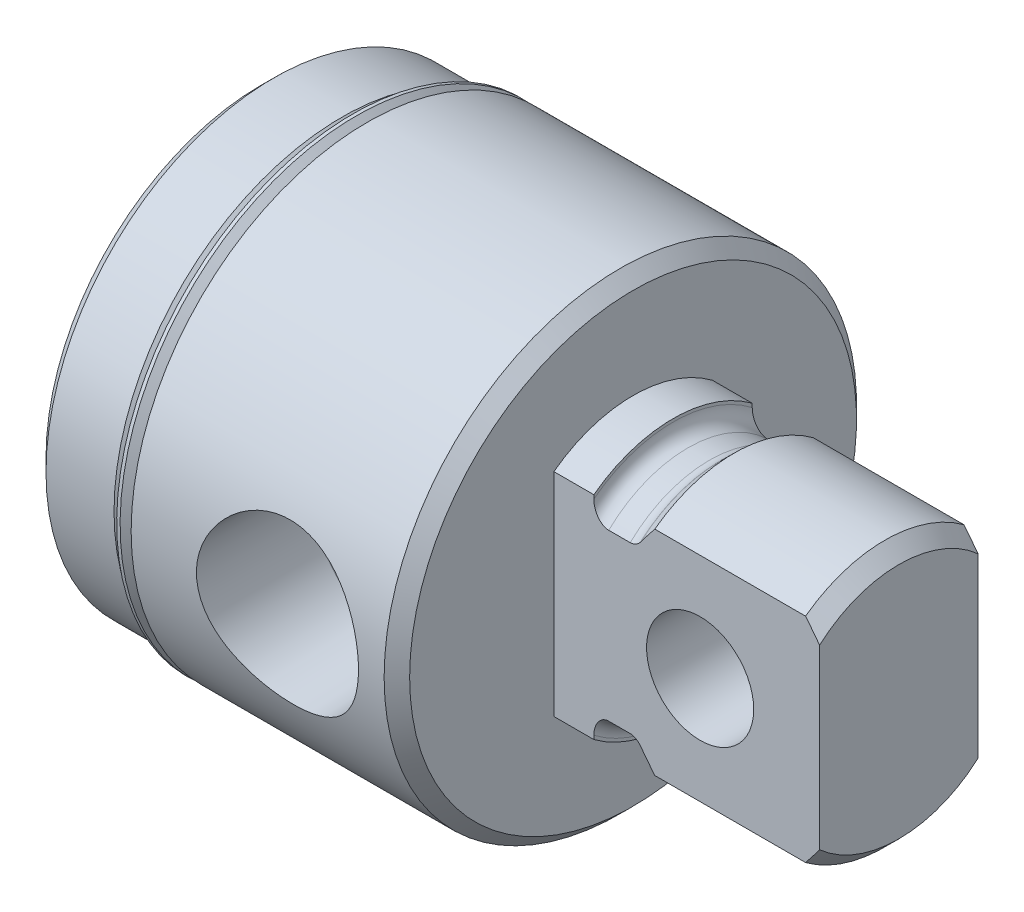
SolidWorks part; units mm, degrees
material "Cast Alloy Steel"
ref_plane "Front Plane" through (0, 0, 0) normal (0, 0, 1) x (1, 0, 0)
ref_plane "Top Plane" through (0, 0, 0) normal (0, 1, 0) x (1, 0, 0)
ref_plane "Right Plane" through (0, 0, 0) normal (1, 0, 0) x (0, 0, -1)
ref_plane "Plane1" through (38.1, 0, 0) normal (1, 0, 0) x (0, 0, -1)
sketch "Sketch1" plane through (0, 0, 0) normal (0, 0, 1) x (1, 0, 0)
  line L0 (0, 0) -> (0, 12.846)
  line L1 (0, 12.846) -> (0.762, 13.6081)
  line L2 (0.762, 13.6081) -> (4.826, 13.6081)
  line L3 (4.826, 13.6081) -> (5.588, 12.846)
  line L4 (5.588, 12.846) -> (6.35, 12.846)
  line L5 (6.35, 12.846) -> (6.35, 14.1097)
  line L6 (6.35, 14.1097) -> (21.463, 14.1097)
  line L7 (21.463, 14.1097) -> (22.225, 13.3477)
  line L8 (22.225, 13.3477) -> (22.225, 0)
  line L9 (22.225, 0) -> (0, 0)
  line L10 (22.225, 0) -> (0, 0) construction
revolve "Revolve1" add sketch "Sketch1" angle 360 about L10 reverse direction yes
sketch "Sketch2" plane through (0, 0, 0) normal (0, 0, 1) x (1, 0, 0)
  line L0 (22.225, 0) -> (22.225, 7.9057)
  line L1 (22.225, 7.9057) -> (24.6126, 7.9057)
  line L2 (24.6126, 7.9057) -> (24.6126, 7.7279)
  line L3 (25.5016, 6.8389) -> (26.7843, 6.8389)
  line L4 (27.383, 7.0708) -> (27.4129, 7.098)
  line L5 (27.4129, 7.098) -> (28.2524, 7.9375)
  line L6 (28.2524, 7.9375) -> (37.2605, 7.9375)
  line L7 (37.2605, 7.9375) -> (38.1, 7.098)
  line L8 (38.1, 7.098) -> (38.1, 0)
  line L9 (38.1, 0) -> (22.225, 0)
  line L10 (38.1, 0) -> (22.225, 0) construction
  arc A0 (24.6126, 7.7279) -> (25.5016, 6.8389) centre (25.5016, 7.7279) ccw
  arc A1 (26.7843, 6.8389) -> (27.383, 7.0708) centre (26.7843, 7.7279) ccw
revolve "Revolve2" add sketch "Sketch2" angle 360 about L10 reverse direction yes
cosmetic thread "Cosmetic Thread1" parameters "D1"=10.6871, "D2"=14.1961
sketch "Sketch3" plane through (38.1, 0, 0) normal (1, 0, 0) x (0, 0, -1)
  line L0 (-28.2194, -56.4388) -> (28.2194, -56.4388)
  line L1 (28.2194, -56.4388) -> (28.2194, 56.4388)
  line L2 (28.2194, 56.4388) -> (-28.2194, 56.4388)
  line L3 (-28.2194, 56.4388) -> (-28.2194, -56.4388)
  line L4 (-4.7307, -28.2194) -> (4.7307, -28.2194)
  line L5 (4.7307, -28.2194) -> (4.7307, 28.2194)
  line L6 (4.7307, 28.2194) -> (-4.7307, 28.2194)
  line L7 (-4.7307, 28.2194) -> (-4.7307, -28.2194)
extrude "Cut-Extrude1" cut sketch "Sketch3" against normal blind 15.875
ref_plane "Plane2" through (22.225, 0, 0) normal (1, 0, 0) x (0, 0, -1)
hole_wizard "Hole1" positions "Sketch5" profile "Sketch4" legacy
sketch "Sketch5" plane through (0, 0, 0) normal (-1, 0, 0) x (0, 0, 1)
  point P0 (0, 0)
sketch "Sketch4" plane through (0, 0, 0) normal (0, 1, 0) x (0, 0, 1)
  line L0 (0, 0) -> (0, 23.7046)
  line L1 (0, 23.7046) -> (4.7625, 20.955)
  line L2 (4.7625, 20.955) -> (4.7625, 0)
  line L4 (4.7625, 0) -> (0, 0)
  line L6 (0, 23.7046) -> (-4.7625, 20.955) construction
  line L7 (0, -4.2442) -> (0, 117.3081) construction
  dimension "Diameter" = 9.525
  dimension "Depth" = 20.955
  dimension "Drill Angle" = 120
ref_plane "Plane3" through (0, 0, 0) normal (0, 0.9998, 0.0175) x (1, 0, 0)
sketch "Sketch6" plane through (0, 0, 0) normal (0, 0.9998, 0.0175) x (1, 0, 0)
  line L0 (15.0876, 0) -> (19.7106, 0)
  line L1 (19.7106, 0) -> (19.7106, -7.1755)
  line L2 (19.7106, -7.1755) -> (19.9271, -14.1097)
  line L3 (19.9271, -14.1097) -> (15.0876, -14.1097)
  line L4 (15.0876, -14.1097) -> (15.0876, 0)
  line L5 (15.0876, -14.1097) -> (15.0876, 0) construction
revolve "Cut-Revolve1" cut sketch "Sketch6" angle 360 about L5 reverse direction yes
cosmetic thread "Cosmetic Thread2" parameters "D1"=6.9342, "D2"=10.287
ref_plane "Plane4" through (15.0876, 0, 0) normal (1, 0, 0) x (0, 0, -1)
ref_plane "Plane5" through (5.588, 0, 0) normal (1, 0, 0) x (0, 0, -1)
sketch "Sketch7" plane through (0, 0, 0) normal (0, 0, 1) x (1, 0, 0)
  line L0 (5.4861, 14.0255) -> (6.2275, 13.2842)
  line L1 (6.2275, 13.1046) -> (5.969, 12.846)
  line L2 (5.969, 12.846) -> (5.588, 12.846)
  line L3 (5.588, 12.846) -> (5.588, 12.592)
  line L4 (5.588, 12.592) -> (6.35, 12.592)
  line L5 (6.35, 12.592) -> (6.35, 13.449)
  line L6 (6.35, 13.449) -> (5.6893, 14.1097)
  line L7 (5.6893, 14.1097) -> (5.4861, 14.1097)
  line L8 (5.4861, 14.1097) -> (5.4861, 14.0255)
  line L9 (6.35, 0) -> (5.588, 0) construction
  arc A0 (6.2275, 13.2842) -> (6.2275, 13.1046) centre (6.1377, 13.1944) cw
revolve "Revolve3" add sketch "Sketch7" angle 360 about L9 reverse direction yes
ref_plane "Plane6" through (38.227, 0, 0) normal (1, 0, 0) x (0, 0, -1)
sketch "Sketch8" plane through (0, 0, 0) normal (0, 0, 1) x (1, 0, 0)
  circle A0 centre (30.9626, 0) radius 3.2004
extrude "Cut-Extrude2" cut sketch "Sketch8" along normal blind 7.0961 and the other way blind 7.0961
ref_plane "Plane7" through (24.6126, 0, 0) normal (1, 0, 0) x (0, 0, -1)
ref_plane "Plane8" through (33.3248, 0, 0) normal (1, 0, 0) x (0, 0, -1)
ref_plane "Plane9" through (30.9626, 0, 0) normal (1, 0, 0) x (0, 0, -1)
ref_plane "Plane10" through (38.1, 0, 0) normal (1, 0, 0) x (0, 0, -1)
ref_plane "Plane11" through (0, 0, 0) normal (0, 0, 1) x (1, 0, 0)
ref_plane "Plane12" through (24.6126, 0, 0) normal (1, 0, 0) x (0, 0, -1)
ref_plane "Plane13" through (0, 0, 0) normal (0, 1, 0) x (1, 0, 0)
ref_plane "Plane14" through (0, 10.2743, 0) normal (0, 1, 0) x (1, 0, 0)
ref_plane "Plane15" through (22.225, 0, 0) normal (1, 0, 0) x (0, 0, -1)
ref_plane "1 XY" through (24.6126, 0, 0) normal (1, 0, 0) x (0, 0, -1)
ref_plane "1 XZ" through (0, 0, 0) normal (0, -1, 0) x (-1, 0, 0)
ref_plane "1 YZ" through (0, 0, 0) normal (0, 0, -1) x (-1, 0, 0)
ref_axis "1 X" through (24.6126, 0, 80.9) along (0, 0, -1)
ref_axis "1 Y" through (24.6126, -50, 0) along (0, 1, 0)
ref_axis "1 Z" through (80.9, 0, 0) along (-1, 0, 0)
sketch3d "1"
  point P0 (24.6126, 0, 0)
ref_plane "c1 XY" through (0, 0, 0) normal (0, 0, 1) x (1, 0, 0)
ref_plane "c1 XZ" through (0, 7.9057, 0) normal (0, -1, 0) x (-1, 0, 0)
ref_plane "c1 YZ" through (22.225, 0, 0) normal (1, 0, 0) x (0, 0, -1)
ref_axis "c1 X" through (-80.9, 7.9057, 0) along (1, 0, 0)
ref_axis "c1 Y" through (22.225, -50, 0) along (0, 1, 0)
ref_axis "c1 Z" through (22.225, 7.9057, 80.9) along (0, 0, -1)
sketch3d "c1"
  point P0 (22.225, 7.9057, 0)
ref_plane "c2 XY" through (0, 0, 0) normal (0, 0, 1) x (1, 0, 0)
ref_plane "c2 XZ" through (0, -7.9057, 0) normal (0, -1, 0) x (-1, 0, 0)
ref_plane "c2 YZ" through (22.225, 0, 0) normal (1, 0, 0) x (0, 0, -1)
ref_axis "c2 X" through (-80.9, -7.9057, 0) along (1, 0, 0)
ref_axis "c2 Y" through (22.225, -50, 0) along (0, 1, 0)
ref_axis "c2 Z" through (22.225, -7.9057, 80.9) along (0, 0, -1)
sketch3d "c2"
  point P0 (22.225, -7.9057, 0)
ref_plane "cc1 XY" through (0, 0, 0) normal (0, 0, 1) x (1, 0, 0)
ref_plane "cc1 XZ" through (0, 0, 0) normal (0, -1, 0) x (-1, 0, 0)
ref_plane "cc1 YZ" through (22.225, 0, 0) normal (1, 0, 0) x (0, 0, -1)
ref_axis "cc1 X" through (-80.9, 0, 0) along (1, 0, 0)
ref_axis "cc1 Y" through (22.225, -50, 0) along (0, 1, 0)
ref_axis "cc1 Z" through (22.225, 0, 80.9) along (0, 0, -1)
sketch3d "cc1"
  point P0 (22.225, 0, 0)
ref_plane "cc2 XY" through (0, 0, 0) normal (0, 0, 1) x (1, 0, 0)
ref_plane "cc2 XZ" through (0, 0, 0) normal (0, -1, 0) x (-1, 0, 0)
ref_plane "cc2 YZ" through (24.6126, 0, 0) normal (1, 0, 0) x (0, 0, -1)
ref_axis "cc2 X" through (-80.9, 0, 0) along (1, 0, 0)
ref_axis "cc2 Y" through (24.6126, -50, 0) along (0, 1, 0)
ref_axis "cc2 Z" through (24.6126, 0, 80.9) along (0, 0, -1)
sketch3d "cc2"
  point P0 (24.6126, 0, 0)
ref_plane "lovra1 XY" through (33.3248, 0, 0) normal (1, 0, 0) x (0, 0, -1)
ref_plane "lovra1 XZ" through (0, 0, 0) normal (0, -1, 0) x (-1, 0, 0)
ref_plane "lovra1 YZ" through (0, 0, 0) normal (0, 0, -1) x (-1, 0, 0)
ref_axis "lovra1 X" through (33.3248, 0, 80.9) along (0, 0, -1)
ref_axis "lovra1 Y" through (33.3248, -50, 0) along (0, 1, 0)
ref_axis "lovra1 Z" through (80.9, 0, 0) along (-1, 0, 0)
sketch3d "lovra1"
  point P0 (33.3248, 0, 0)
ref_plane "lovra2 XY" through (33.3248, 0, 0) normal (1, 0, 0) x (0, 0, -1)
ref_plane "lovra2 XZ" through (0, 11.049, 0) normal (0, -1, 0) x (-1, 0, 0)
ref_plane "lovra2 YZ" through (0, 0, 0) normal (0, 0, -1) x (-1, 0, 0)
ref_axis "lovra2 X" through (33.3248, 11.049, 80.9) along (0, 0, -1)
ref_axis "lovra2 Y" through (33.3248, -50, 0) along (0, 1, 0)
ref_axis "lovra2 Z" through (80.9, 11.049, 0) along (-1, 0, 0)
sketch3d "lovra2"
  point P0 (33.3248, 11.049, 0)
ref_plane "lovra21 XY" through (0, 0, 0) normal (1, 0, 0) x (0, 0, -1)
ref_plane "lovra21 XZ" through (0, 0, 0) normal (0, -1, 0) x (-1, 0, 0)
ref_plane "lovra21 YZ" through (0, 0, 5.2705) normal (0, 0, -1) x (-1, 0, 0)
ref_axis "lovra21 X" through (0, 0, 80.9) along (0, 0, -1)
ref_axis "lovra21 Y" through (0, -50, 5.2705) along (0, 1, 0)
ref_axis "lovra21 Z" through (80.9, 0, 5.2705) along (-1, 0, 0)
sketch3d "lovra21"
  point P0 (0, 0, 5.2705)
ref_plane "lovra22 XY" through (0, 0, 0) normal (1, 0, 0) x (0, 0, -1)
ref_plane "lovra22 XZ" through (0, 0, 0) normal (0, -1, 0) x (-1, 0, 0)
ref_plane "lovra22 YZ" through (0, 0, -5.2705) normal (0, 0, -1) x (-1, 0, 0)
ref_axis "lovra22 X" through (0, 0, 80.9) along (0, 0, -1)
ref_axis "lovra22 Y" through (0, -50, -5.2705) along (0, 1, 0)
ref_axis "lovra22 Z" through (80.9, 0, -5.2705) along (-1, 0, 0)
sketch3d "lovra22"
  point P0 (0, 0, -5.2705)
ref_plane "lovra3 XY" through (33.3248, 0, 0) normal (1, 0, 0) x (0, 0, -1)
ref_plane "lovra3 XZ" through (0, -11.049, 0) normal (0, -1, 0) x (-1, 0, 0)
ref_plane "lovra3 YZ" through (0, 0, 0) normal (0, 0, -1) x (-1, 0, 0)
ref_axis "lovra3 X" through (33.3248, -11.049, 80.9) along (0, 0, -1)
ref_axis "lovra3 Y" through (33.3248, -50, 0) along (0, 1, 0)
ref_axis "lovra3 Z" through (80.9, -11.049, 0) along (-1, 0, 0)
sketch3d "lovra3"
  point P0 (33.3248, -11.049, 0)
ref_plane "olen XY" through (30.9626, 0, 0) normal (1, 0, 0) x (0, 0, -1)
ref_plane "olen XZ" through (0, 0, 0) normal (0, -1, 0) x (-1, 0, 0)
ref_plane "olen YZ" through (0, 0, 0) normal (0, 0, -1) x (-1, 0, 0)
ref_axis "olen X" through (30.9626, 0, 80.9) along (0, 0, -1)
ref_axis "olen Y" through (30.9626, -50, 0) along (0, 1, 0)
ref_axis "olen Z" through (80.9, 0, 0) along (-1, 0, 0)
sketch3d "olen"
  point P0 (30.9626, 0, 0)
ref_plane "p1 XY" through (38.1, 0, 0) normal (1, 0, 0) x (0, 0, -1)
ref_plane "p1 XZ" through (0, 0, 0) normal (0, -1, 0) x (-1, 0, 0)
ref_plane "p1 YZ" through (0, 0, 4.7307) normal (0, 0, -1) x (-1, 0, 0)
ref_axis "p1 X" through (38.1, 0, 80.9) along (0, 0, -1)
ref_axis "p1 Y" through (38.1, -50, 4.7307) along (0, 1, 0)
ref_axis "p1 Z" through (80.9, 0, 4.7307) along (-1, 0, 0)
sketch3d "p1"
  point P0 (38.1, 0, 4.7307)
ref_plane "p2 XY" through (38.1, 0, 0) normal (1, 0, 0) x (0, 0, -1)
ref_plane "p2 XZ" through (0, 0, 0) normal (0, -1, 0) x (-1, 0, 0)
ref_plane "p2 YZ" through (0, 0, -4.7307) normal (0, 0, -1) x (-1, 0, 0)
ref_axis "p2 X" through (38.1, 0, 80.9) along (0, 0, -1)
ref_axis "p2 Y" through (38.1, -50, -4.7307) along (0, 1, 0)
ref_axis "p2 Z" through (80.9, 0, -4.7307) along (-1, 0, 0)
sketch3d "p2"
  point P0 (38.1, 0, -4.7307)
ref_plane "port XY" through (0, 0, 0) normal (0, 0, 1) x (1, 0, 0)
ref_plane "port XZ" through (0, 0, 0) normal (0, -1, 0) x (-1, 0, 0)
ref_plane "port YZ" through (15.0876, 0, 0) normal (1, 0, 0) x (0, 0, -1)
ref_axis "port X" through (-80.9, 0, 0) along (1, 0, 0)
ref_axis "port Y" through (15.0876, -50, 0) along (0, 1, 0)
ref_axis "port Z" through (15.0876, 0, 80.9) along (0, 0, -1)
sketch3d "port"
  point P0 (15.0876, 0, 0)
ref_plane "port2 XY" through (38.1, 0, 0) normal (1, 0, 0) x (0, 0, -1)
ref_plane "port2 XZ" through (0, 0, 0) normal (0, -1, 0) x (-1, 0, 0)
ref_plane "port2 YZ" through (0, 0, 0) normal (0, 0, -1) x (-1, 0, 0)
ref_axis "port2 X" through (38.1, 0, 80.9) along (0, 0, -1)
ref_axis "port2 Y" through (38.1, -50, 0) along (0, 1, 0)
ref_axis "port2 Z" through (80.9, 0, 0) along (-1, 0, 0)
sketch3d "port2"
  point P0 (38.1, 0, 0)
ref_plane "thd1 XY" through (38.1, 0, 0) normal (1, 0, 0) x (0, 0, -1)
ref_plane "thd1 XZ" through (0, 0, 0) normal (0, -1, 0) x (-1, 0, 0)
ref_plane "thd1 YZ" through (0, 0, 7.9375) normal (0, 0, -1) x (-1, 0, 0)
ref_axis "thd1 X" through (38.1, 0, 80.9) along (0, 0, -1)
ref_axis "thd1 Y" through (38.1, -50, 7.9375) along (0, 1, 0)
ref_axis "thd1 Z" through (80.9, 0, 7.9375) along (-1, 0, 0)
sketch3d "thd1"
  point P0 (38.1, 0, 7.9375)
ref_plane "thd2 XY" through (38.1, 0, 0) normal (1, 0, 0) x (0, 0, -1)
ref_plane "thd2 XZ" through (0, 0, 0) normal (0, -1, 0) x (-1, 0, 0)
ref_plane "thd2 YZ" through (0, 0, -7.9375) normal (0, 0, -1) x (-1, 0, 0)
ref_axis "thd2 X" through (38.1, 0, 80.9) along (0, 0, -1)
ref_axis "thd2 Y" through (38.1, -50, -7.9375) along (0, 1, 0)
ref_axis "thd2 Z" through (80.9, 0, -7.9375) along (-1, 0, 0)
sketch3d "thd2"
  point P0 (38.1, 0, -7.9375)
ref_plane "to_mounting_bracket XY" through (22.225, 0, 0) normal (1, 0, 0) x (0, 0, -1)
ref_plane "to_mounting_bracket XZ" through (0, 0, 0) normal (0, -1, 0) x (-1, 0, 0)
ref_plane "to_mounting_bracket YZ" through (0, 0, 0) normal (0, 0, -1) x (-1, 0, 0)
ref_axis "to_mounting_bracket X" through (22.225, 0, 80.9) along (0, 0, -1)
ref_axis "to_mounting_bracket Y" through (22.225, -50, 0) along (0, 1, 0)
ref_axis "to_mounting_bracket Z" through (80.9, 0, 0) along (-1, 0, 0)
sketch3d "to_mounting_bracket"
  point P0 (22.225, 0, 0)
ref_plane "to_nut XY" through (24.6126, 0, 0) normal (1, 0, 0) x (0, 0, -1)
ref_plane "to_nut XZ" through (0, 0, 0) normal (0, -1, 0) x (-1, 0, 0)
ref_plane "to_nut YZ" through (0, 0, 0) normal (0, 0, -1) x (-1, 0, 0)
ref_axis "to_nut X" through (24.6126, 0, 80.9) along (0, 0, -1)
ref_axis "to_nut Y" through (24.6126, -50, 0) along (0, 1, 0)
ref_axis "to_nut Z" through (80.9, 0, 0) along (-1, 0, 0)
sketch3d "to_nut"
  point P0 (24.6126, 0, 0)
ref_plane "to_pin XY" through (0, 0, 0) normal (0, 0, 1) x (1, 0, 0)
ref_plane "to_pin XZ" through (0, 0, 0) normal (0, -1, 0) x (-1, 0, 0)
ref_plane "to_pin YZ" through (30.9626, 0, 0) normal (1, 0, 0) x (0, 0, -1)
ref_axis "to_pin X" through (-80.9, 0, 0) along (1, 0, 0)
ref_axis "to_pin Y" through (30.9626, -50, 0) along (0, 1, 0)
ref_axis "to_pin Z" through (30.9626, 0, 80.9) along (0, 0, -1)
sketch3d "to_pin"
  point P0 (30.9626, 0, 0)
ref_plane "to_screw XY" through (0, 10.2743, 0) normal (0, 1, 0) x (1, 0, 0)
ref_plane "to_screw XZ" through (0, 0, -7.0612) normal (0, 0, 1) x (1, 0, 0)
ref_plane "to_screw YZ" through (15.0876, 0, 0) normal (1, 0, 0) x (0, 0, -1)
ref_axis "to_screw X" through (-80.9, 10.2743, -7.0612) along (1, 0, 0)
ref_axis "to_screw Y" through (15.0876, 10.2743, 50) along (0, 0, -1)
ref_axis "to_screw Z" through (15.0876, 50, -7.0612) along (0, -1, 0)
sketch3d "to_screw"
  point P0 (15.0876, 10.2743, -7.0612)
ref_plane "to_tube XY" through (5.588, 0, 0) normal (1, 0, 0) x (0, 0, -1)
ref_plane "to_tube XZ" through (0, 0, 0) normal (0, -1, 0) x (-1, 0, 0)
ref_plane "to_tube YZ" through (0, 0, 0) normal (0, 0, -1) x (-1, 0, 0)
ref_axis "to_tube X" through (5.588, 0, 80.9) along (0, 0, -1)
ref_axis "to_tube Y" through (5.588, -50, 0) along (0, 1, 0)
ref_axis "to_tube Z" through (80.9, 0, 0) along (-1, 0, 0)
sketch3d "to_tube"
  point P0 (5.588, 0, 0)
